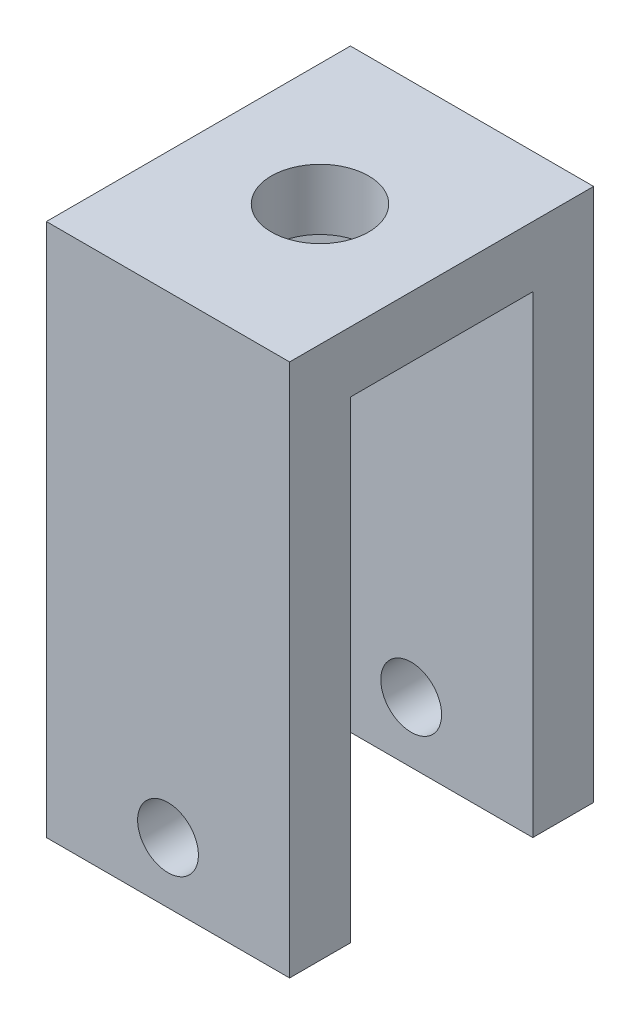
SolidWorks part; units mm, degrees
material "AISI 1035 Acier (SS)"
ref_plane "Plan de face" through (0, 0, 0) normal (0, 0, 1) x (1, 0, 0)
ref_plane "Plan de dessus" through (0, 0, 0) normal (0, 1, 0) x (1, 0, 0)
ref_plane "Plan de droite" through (0, 0, 0) normal (1, 0, 0) x (0, 0, -1)
sketch "Esquisse1" plane through (0, 0, 0) normal (0, 0, 1) x (1, 0, 0)
  line L0 (4, 0) -> (-4, 0)
  line L1 (4, 0) -> (4, 17.55)
  line L6 (0, 12) -> (0, 0) construction
  line L9 (-4, 0) -> (-4, 17.55)
  line L10 (4, 17.55) -> (-4, 17.55)
  dimension "D1" = 17.55
  dimension "D3" = 4
extrude "Boss.-Extru.1" add sketch "Esquisse1" along normal blind 10
sketch "Esquisse2" plane through (4, 0, 0) normal (1, 0, 0) x (0, 0, -1)
  line L0 (-10, 0) -> (0, 0) construction
  line L1 (-8, 0) -> (-2, 0)
  line L2 (-8, 0) -> (-8, 15.55)
  line L3 (-8, 15.55) -> (-2, 15.55)
  line L4 (-2, 0) -> (-2, 15.55)
  line L5 (-10, 17.55) -> (0, 17.55) construction
  dimension "D1" = 2
  dimension "D2" = 2
  dimension "D3" = 2
extrude "Enlèv. mat.-Extru.1" cut sketch "Esquisse2" against normal through all
sketch "Esquisse3" plane through (0, 0, 0) normal (0, 0, -1) x (-1, 0, 0)
  circle A0 centre (0, 2) radius 1
  dimension "D2" = 2
  dimension "D1" = 2
extrude "Enlèv. mat.-Extru.2" cut sketch "Esquisse3" against normal through all
sketch "Esquisse5" plane through (0, 15.55, 0) normal (0, -1, 0) x (1, 0, 0)
  line L0 (0, 8) -> (0, 2) construction
  line L1 (-4, 8) -> (4, 8) construction
  line L2 (-4, 2) -> (4, 2) construction
  circle A0 centre (0, 5) radius 1.6
  dimension "D1" = 3.2
extrude "Enlèv. mat.-Extru.3" cut sketch "Esquisse5" against normal through all
